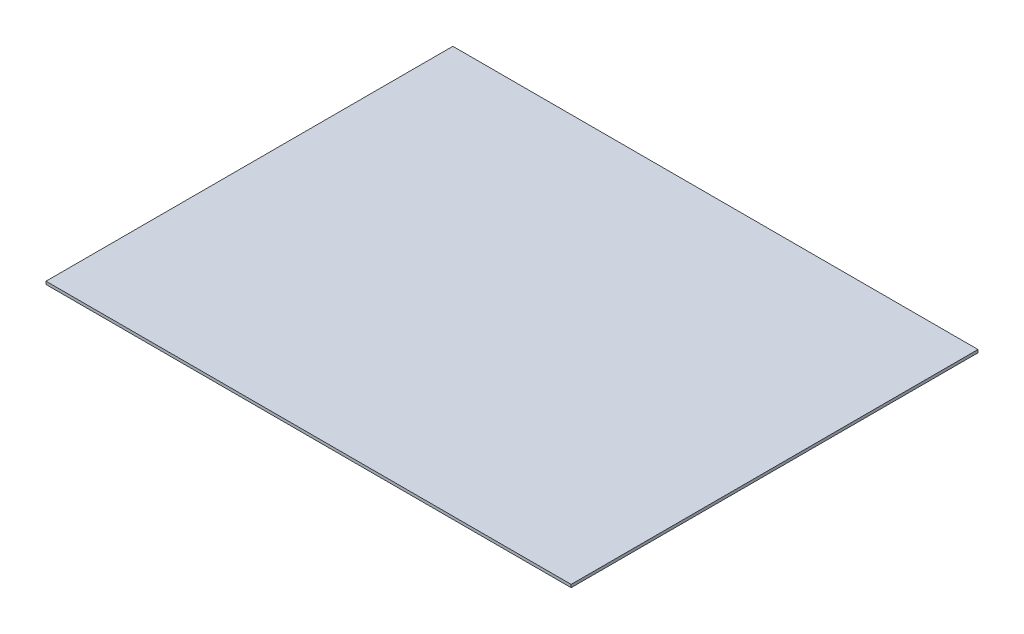
SolidWorks part; units mm, degrees
ref_plane "Front Plane" through (0, 0, 0) normal (0, 0, 1) x (1, 0, 0)
ref_plane "Top Plane" through (0, 0, 0) normal (0, 1, 0) x (1, 0, 0)
ref_plane "Right Plane" through (0, 0, 0) normal (1, 0, 0) x (0, 0, -1)
sketch "Sketch1" plane through (0, 0, 0) normal (0, 1, 0) x (1, 0, 0)
  line L1 (-91, -70.5) -> (91, -70.5)
  line L2 (-91, -70.5) -> (-91, 70.5)
  line L3 (-91, 70.5) -> (91, 70.5)
  line L4 (91, -70.5) -> (91, 70.5)
  line L5 (-91, -70.5) -> (91, 70.5) construction
  line L6 (-91, 70.5) -> (91, -70.5) construction
  point P0 (0, 0)
  dimension "D1" = 182
  dimension "D2" = 141
extrude "Boss-Extrude1" add sketch "Sketch1" along normal blind 1
